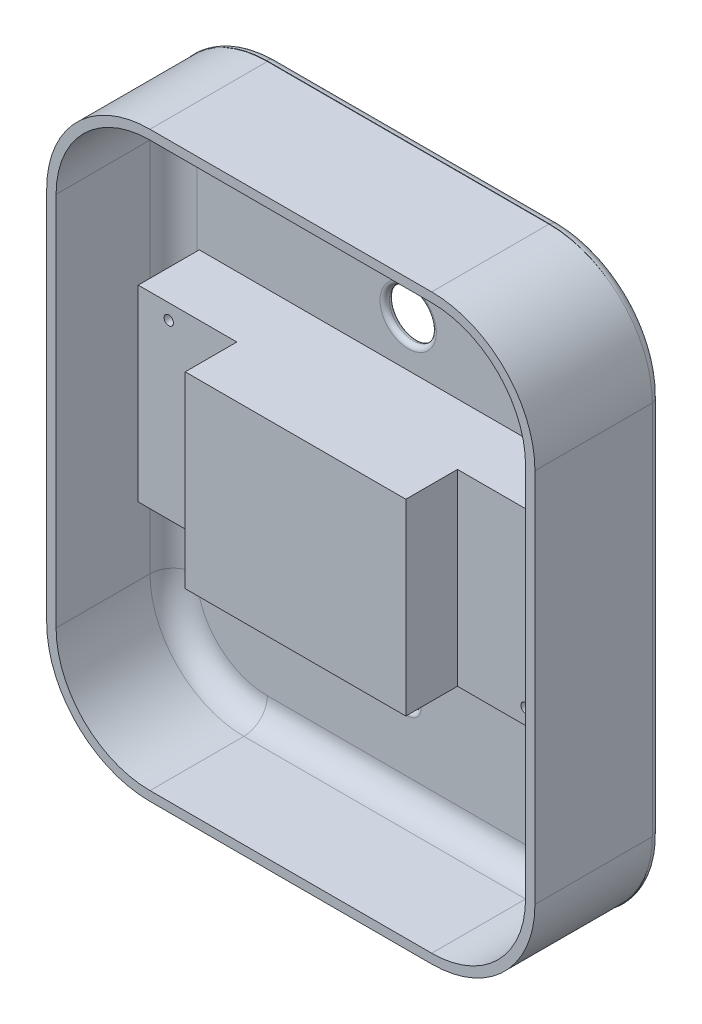
SolidWorks part; units mm, degrees
ref_plane "Front Plane" through (0, 0, 0) normal (0, 0, 1) x (1, 0, 0)
ref_plane "Top Plane" through (0, 0, 0) normal (0, 1, 0) x (1, 0, 0)
ref_plane "Right Plane" through (0, 0, 0) normal (1, 0, 0) x (0, 0, -1)
sketch "Wall Backing" plane through (0, 0, 0) normal (0, 0, 1) x (1, 0, 0)
  line L1 (-37.5, 55) -> (37.5, 55)
  line L2 (-37.5, 55) -> (-37.5, -55)
  line L3 (-37.5, -55) -> (37.5, -55)
  line L4 (37.5, 55) -> (37.5, -55)
  line L5 (-28.5, 50) -> (28.5, 50)
  line L6 (-28.5, 50) -> (-28.5, -50)
  line L7 (-28.5, -50) -> (28.5, -50)
  line L8 (28.5, 50) -> (28.5, -50)
  point P4 (-37.5, 0)
  point P6 (0, 55)
  point P11 (0, 50)
  point P12 (-28.5, 0)
  dimension "D1" = 75
  dimension "D2" = 110
  dimension "D3" = 57
  dimension "D4" = 100
sketch "Case Sides" plane through (0, 0, 0) normal (0, 0, 1) x (1, 0, 0)
  line L0 (0, 60) -> (0, -60) construction
  line L5 (-30, 60) -> (30, 60)
  line L6 (-50, 40) -> (-50, -40)
  line L7 (-30, -60) -> (30, -60)
  line L8 (50, 40) -> (50, -40)
  line L9 (-50, 0) -> (50, 0) construction
  line L10 (-30, 62) -> (30, 62)
  line L11 (52, 40) -> (52, -40)
  line L12 (-30, -62) -> (30, -62)
  line L13 (-52, 40) -> (-52, -40)
  arc A2 (50, 40) -> (30, 60) centre (30, 40) ccw
  arc A3 (50, -40) -> (30, -60) centre (30, -40) cw
  arc A4 (-30, -60) -> (-50, -40) centre (-30, -40) cw
  arc A5 (-50, 40) -> (-30, 60) centre (-30, 40) cw
  arc A6 (52, 40) -> (30, 62) centre (30, 40) ccw
  arc A7 (52, -40) -> (30, -62) centre (30, -40) cw
  arc A8 (-30, -62) -> (-52, -40) centre (-30, -40) cw
  arc A9 (-52, 40) -> (-30, 62) centre (-30, 40) cw
  point P17 (50, 60)
  point P23 (-50, -60)
  point P26 (-50, 60)
  dimension "D5" = 20
  dimension "D3" = 100
  dimension "D4" = 120
  dimension "D6" = 2
sketch "Case Bottom" plane through (0, 0, 0) normal (0, 0, 1) x (1, 0, 0)
  line L0 (-30.1664, 62.1012) -> (30.1664, 62.1012)
  line L1 (51.8136, 39.8409) -> (51.8136, -39.8409)
  line L2 (-30.2679, -61.8723) -> (30.2679, -61.8723)
  line L3 (-52.1862, 40.0195) -> (-52.1862, -40.0195)
  line L4 (0, 41) -> (0, 0) construction
  line L5 (0, 0) -> (0, -41) construction
  line L6 (0, -30) -> (0, 0) construction
  line L7 (0, 30) -> (0, 0) construction
  arc A0 (51.8136, 39.8409) -> (30.1664, 62.1012) centre (29.8858, 40.1727) ccw
  arc A1 (51.8136, -39.8409) -> (30.2679, -61.8723) centre (30.6332, -40.6785) cw
  arc A2 (-30.2679, -61.8723) -> (-52.1862, -40.0195) centre (-30.5767, -40.2636) cw
  arc A3 (-52.1862, 40.0195) -> (-30.1664, 62.1012) centre (-29.8045, 39.7205) cw
  circle A4 centre (0, 41) radius 1.75
  circle A5 centre (0, -41) radius 1.75
  circle A6 centre (0, 30) radius 5
  circle A7 centre (0, -30) radius 5
  point P21 (0, 0)
  point P22 (0, 0)
  point P23 (0, 62.1012)
  point P24 (0, -61.8723)
  point P25 (-52.1862, 0)
  point P26 (51.8136, 0)
  point P28 (0, 0)
  point P29 (0, 0)
  dimension "D2" = 3.5
  dimension "D3" = 10
  dimension "D1" = 82
  dimension "D4" = 30
  dimension "D5" = 104
extrude "Boss-Extrude7" add sketch "Case Sides" along normal blind 25
extrude "Boss-Extrude9" add sketch "Case Bottom" against normal blind 2
sketch "Sonoff" plane through (0, 0, 0) normal (0, 0, 1) x (1, 0, 0)
  line L0 (-44.5, -20) -> (-44.5, 20)
  line L1 (-44.5, -20) -> (44.5, -20)
  line L2 (44.5, -20) -> (44.5, 20)
  line L3 (-44.5, 20) -> (44.5, 20)
  line L4 (-44.5, 0) -> (44.5, 0) construction
  line L5 (0, 20) -> (0, -20) construction
  line L6 (-38, 16.75) -> (-38, 0) construction
  line L7 (38, -16.75) -> (38, 0) construction
  line L8 (-38, 16.75) -> (0, 16.75) construction
  line L9 (38, -16.75) -> (0, -16.75) construction
  circle A3 centre (-38, 16.75) radius 1
  circle A4 centre (38, -16.75) radius 1
  dimension "D5" = 2
  dimension "D1" = 89
  dimension "D2" = 40
  dimension "D3" = 76
  dimension "D4" = 33.5
fillet "Fillet1" radius 5 8 edges at (0, -60, 0) (-44.1421, -54.1421, 0) (-50, 0, 0) (-44.1421, 54.1421, 0) (0, 60, 0) (44.1421, 54.1421, 0) (50, 0, 0) (44.1421, -54.1421, 0)
fillet "Fillet2" radius 2 8 edges at (51.8136, 0, -2) (45.6079, 55.4618, -2) (0, 62.1012, -2) (-45.6544, 55.5259, -2) (45.7878, -55.4991, -2) (0, -61.8723, -2) (-45.835, -55.5677, -2) (-52.1862, 0, -2)
fillet "Fillet3" radius 1 8 edges at (1.75, -41, -2) (1.75, -41, 0) (5, -30, -2) (5, -30, 0) (5, 30, 0) (5, 30, -2) (1.75, 41, 0) (1.75, 41, -2)
extrude "Boss-Extrude10" add sketch "Sonoff" along normal blind 13
sketch "Sketch2" plane through (0, 0, 0) normal (0, 0, 1) x (1, 0, 0)
  line L0 (-23.5, -20) -> (-23.5, 20)
  line L1 (-23.5, -20) -> (23.5, -20)
  line L2 (23.5, -20) -> (23.5, 20)
  line L3 (-23.5, 20) -> (23.5, 20)
  point P4 (0, 20)
  point P5 (0, -20)
  dimension "D2" = 40
  dimension "D3" = 47
extrude "Boss-Extrude11" add sketch "Sketch2" along normal blind 24
